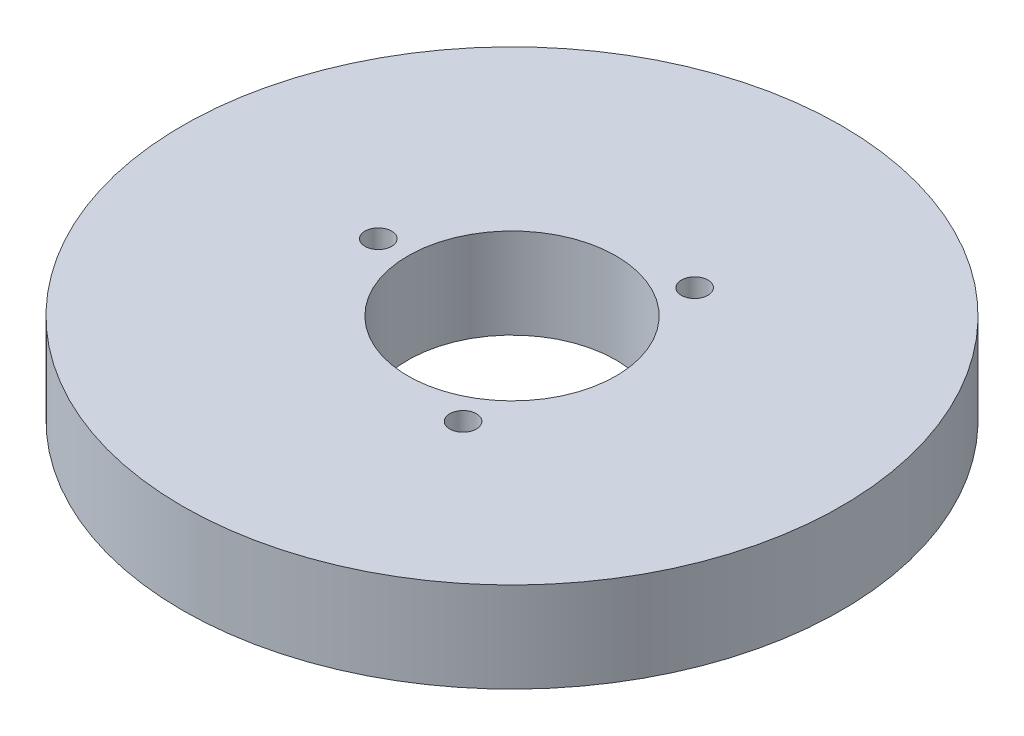
SolidWorks part; units mm, degrees
ref_plane "Front Plane" through (0, 0, 0) normal (0, 0, 1) x (1, 0, 0)
ref_plane "Top Plane" through (0, 0, 0) normal (0, 1, 0) x (1, 0, 0)
ref_plane "Right Plane" through (0, 0, 0) normal (1, 0, 0) x (0, 0, -1)
sketch "Sketch1" plane through (0, 0, 0) normal (0, 1, 0) x (1, 0, 0)
  circle A0 centre (0, 0) radius 47.5
  dimension "FLANGE_OD" = 95
extrude "Boss-Extrude1" add sketch "Sketch1" along normal blind 13
sketch "Sketch2" plane through (0, 0, 0) normal (0, 1, 0) x (1, 0, 0)
  circle A0 centre (0, 0) radius 15
  dimension "BORE_D" = 30
extrude "Cut-Extrude1" cut sketch "Sketch2" along normal through all
sketch "Sketch3" plane through (0, 13, 0) normal (0, 1, 0) x (1, 0, 0)
  circle A0 centre (0, 0) radius 19.2714 construction
  circle A1 centre (-19.2714, 0) radius 1.9169
  dimension "BOLT_D" = 3.8338
  dimension "BOLT_PCD" = 38.5427
extrude "Cut-Extrude2" cut sketch "Sketch3" against normal blind 7.942
pattern_circular "CirPattern1" count 3 over 360 about axis through (0, 0, 0) along (0, 1, 0) of "Cut-Extrude2"
